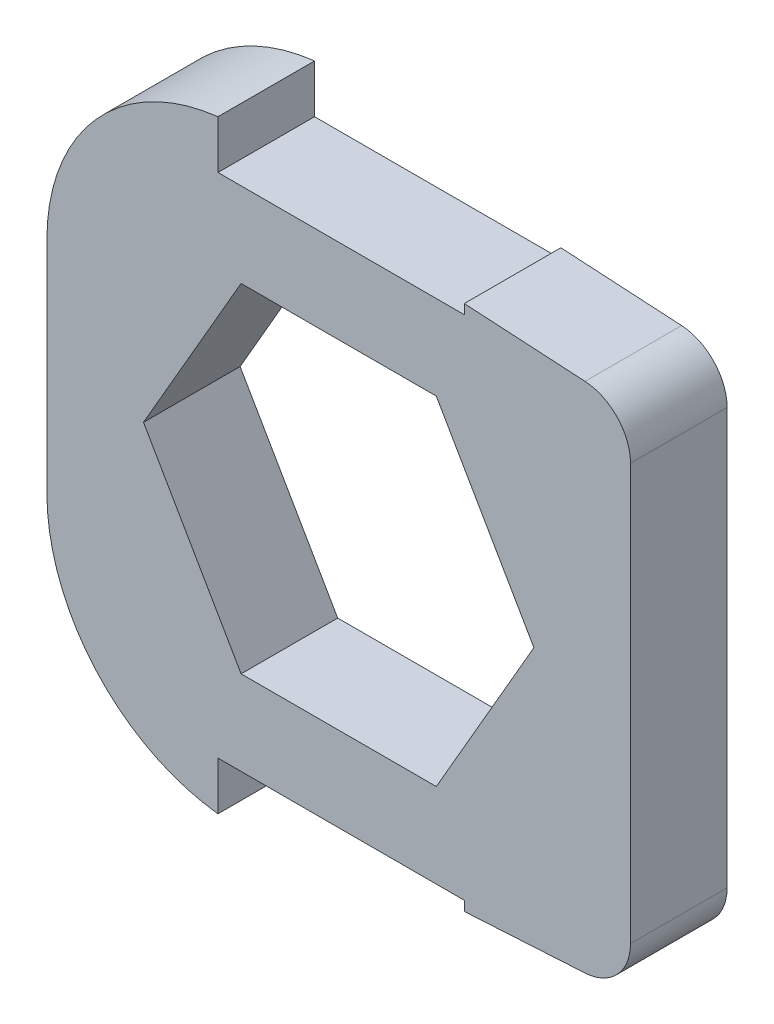
SolidWorks part; units mm, degrees
ref_plane "Plan de face" through (0, 0, 0) normal (0, 0, 1) x (1, 0, 0)
ref_plane "Plan de dessus" through (0, 0, 0) normal (0, 1, 0) x (1, 0, 0)
ref_plane "Plan de droite" through (0, 0, 0) normal (1, 0, 0) x (0, 0, -1)
sketch "Esquisse1" plane through (0, 0, 0) normal (0, 0, 1) x (1, 0, 0)
  line L0 (0, 6.25) -> (3.5415, 6.25)
  line L1 (3.5415, 6.25) -> (3.5415, 5.25)
  line L2 (3.5415, 5.25) -> (12.0829, 5.25) construction
  line L3 (12.0829, 5.25) -> (12.0829, -5.25)
  line L4 (12.0829, -5.25) -> (3.5415, -5.25) construction
  line L5 (3.5415, -5.25) -> (3.5415, -6.25)
  line L6 (3.5415, -6.25) -> (0, -6.25)
  line L7 (0, -6.25) -> (0, 6.25)
  line L8 (0, 0) -> (12.0829, 0) construction
  line L9 (12.0829, 5.25) -> (8.6415, 5.45)
  line L10 (2, 0) -> (4.0207, -3.5)
  line L11 (4.0207, -3.5) -> (8.0622, -3.5)
  line L12 (8.0622, -3.5) -> (10.0829, 0)
  line L13 (10.0829, 0) -> (8.0622, 3.5)
  line L14 (8.0622, 3.5) -> (4.0207, 3.5)
  line L15 (4.0207, 3.5) -> (2, 0)
  line L16 (8.6415, 5.45) -> (8.6415, 5.25)
  line L17 (8.6415, 5.25) -> (3.5415, 5.25)
  line L18 (8.6415, -5.25) -> (3.5415, -5.25)
  line L19 (8.6415, -5.45) -> (8.6415, -5.25)
  line L20 (12.0829, -5.25) -> (8.6415, -5.45)
  circle A0 centre (6.0415, 0) radius 3.5 construction
  dimension "D1" = 7
  dimension "D2" = 1.75
  dimension "D3" = 2.5
  dimension "D4" = 2
  dimension "D5" = 1
  dimension "D6" = 2
  dimension "D7" = 8.0829
  dimension "D8" = 5.1
  dimension "D9" = 0.2
  dimension "D10" = 10.5
extrude "Boss.-Extru.1" add sketch "Esquisse1" along normal blind 2
fillet "Congé1" radius 4 2 edges at (0, -6.25, 1) (0, 6.25, 1)
fillet "Congé2" radius 1 2 edges at (12.0829, -5.25, 1) (12.0829, 5.25, 1)
